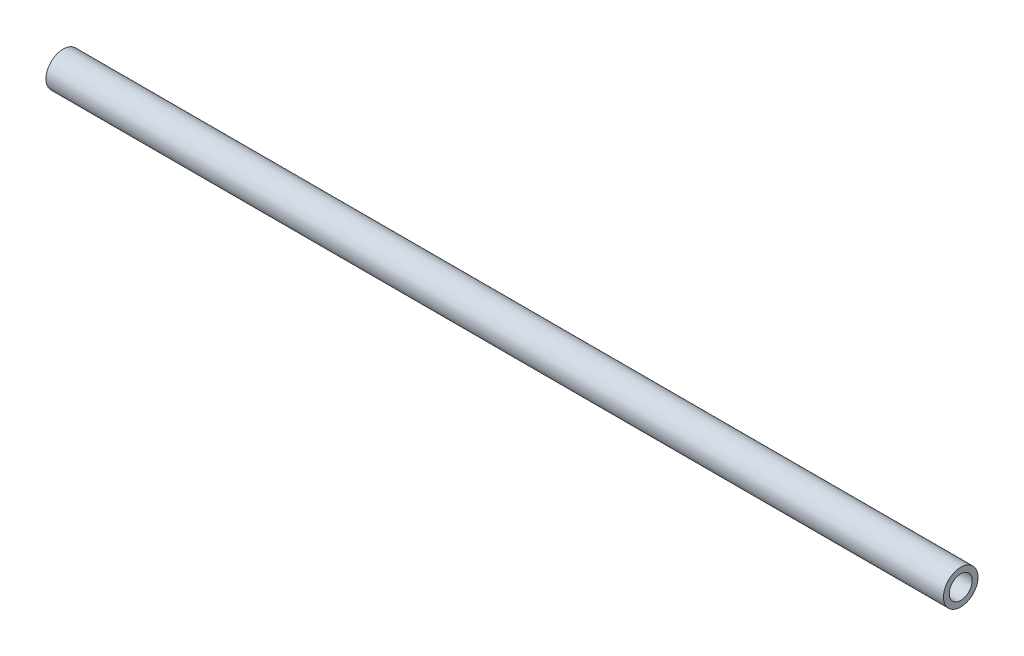
SolidWorks part; units mm, degrees
ref_plane "Front Plane" through (0, 0, 0) normal (0, 0, 1) x (1, 0, 0)
ref_plane "Top Plane" through (0, 0, 0) normal (0, 1, 0) x (1, 0, 0)
ref_plane "Right Plane" through (0, 0, 0) normal (1, 0, 0) x (0, 0, -1)
sketch "Sketch1" plane through (0, 0, 0) normal (1, 0, 0) x (0, 0, -1)
  circle A0 centre (0, 0) radius 9.525
  circle A1 centre (0, 0) radius 6.35
  dimension "D1" = 19.05
  dimension "D2" = 3.175
extrude "Boss-Extrude1" add sketch "Sketch1" against normal blind 495.3 contours A0 A1 region at (0, 0, 9.2556)
move or copy body "Body-Move/Copy1" [suppressed] bodies to move or copy 101 parameters "D1"=0, "D2"=0, "D3"=0
move or copy body "Body-Move/Copy2" [suppressed] bodies to move or copy 102 parameters "D1"=0, "D2"=0, "D3"=0
